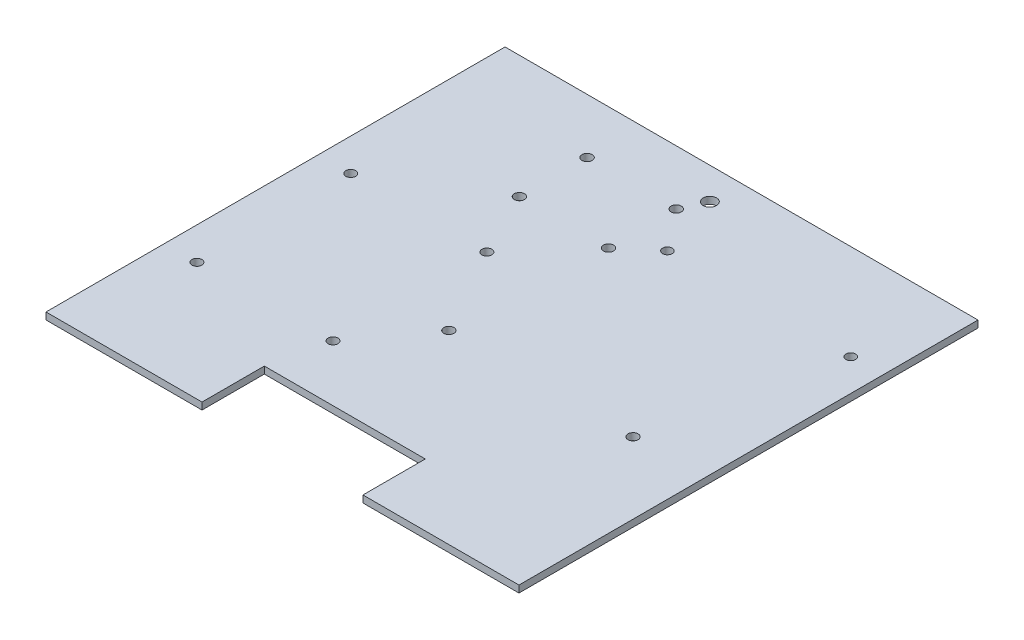
SolidWorks part; units mm, degrees
ref_plane "Front Plane" through (0, 0, 0) normal (0, 0, 1) x (1, 0, 0)
ref_plane "Top Plane" through (0, 0, 0) normal (0, 1, 0) x (1, 0, 0)
ref_plane "Right Plane" through (0, 0, 0) normal (1, 0, 0) x (0, 0, -1)
sketch "Sketch1" plane through (0, 0, 0) normal (0, 1, 0) x (1, 0, 0)
  line L1 (-94.869, -92.075) -> (94.869, -92.075)
  line L2 (-94.869, -92.075) -> (-94.869, 92.075)
  line L3 (-94.869, 92.075) -> (94.869, 92.075)
  line L4 (94.869, -92.075) -> (94.869, 92.075)
  line L5 (-94.869, -92.075) -> (94.869, 92.075) construction
  line L6 (-94.869, 92.075) -> (94.869, -92.075) construction
  point P0 (0, 0)
  dimension "D1" = 189.738
  dimension "D2" = 184.15
extrude "Boss-Extrude1" add sketch "Sketch1" along normal blind 2.794
sketch "Sketch2" plane through (0, 2.794, 0) normal (0, 1, 0) x (1, 0, 0)
  line L2 (94.869, 92.075) -> (-94.869, 92.075) construction
  circle A0 centre (0, 79.375) radius 2.6797
  point P4 (0, 92.075)
  dimension "D1" = 5.3594
  dimension "D2" = 12.7
extrude "Cut-Extrude1" cut sketch "Sketch2" against normal through all
sketch "Sketch3" plane through (0, 2.794, 0) normal (0, 1, 0) x (1, 0, 0)
  line L0 (0, -92.075) -> (-32.28, -92.075)
  line L1 (-94.869, -92.075) -> (94.869, -92.075) construction
  line L2 (-32.28, -92.075) -> (-32.28, -67.075)
  line L3 (-32.28, -67.075) -> (32.28, -67.075)
  line L4 (32.28, -67.075) -> (32.28, -92.075)
  line L5 (32.28, -92.075) -> (0, -92.075)
  point P5 (0, -67.075)
  dimension "D1" = 64.56
  dimension "D3" = 25
extrude "Cut-Extrude2" cut sketch "Sketch3" against normal through all
sketch "Sketch4" plane through (0, 2.794, 0) normal (0, 1, 0) x (1, 0, 0)
  line L7 (-42.851, 73.025) -> (-1.671, 73.025)
  line L8 (-42.851, 73.025) -> (-42.851, 40.025)
  line L9 (-42.851, 40.025) -> (-1.671, 40.025)
  line L10 (-1.671, 73.025) -> (-1.671, 40.025)
  line L11 (-42.851, 73.025) -> (-1.671, 40.025) construction
  line L12 (-42.851, 40.025) -> (-1.671, 73.025) construction
  line L13 (4.679, 79.375) -> (85.979, 79.375)
  line L14 (4.679, 79.375) -> (4.679, 28.355)
  line L15 (4.679, 28.355) -> (85.979, 28.355)
  line L16 (85.979, 79.375) -> (85.979, 28.355)
  line L17 (4.679, 79.375) -> (85.979, 28.355) construction
  line L18 (4.679, 28.355) -> (85.979, 79.375) construction
  line L19 (-42.851, 56.525) -> (-1.671, 56.525) construction
  line L20 (-85.979, -61.067) -> (-85.979, 33.675)
  line L21 (-85.979, 33.675) -> (-23.114, 33.675)
  line L22 (-23.114, 33.675) -> (-23.114, -61.067)
  line L23 (-23.114, -61.067) -> (-85.979, -61.067)
  line L24 (94.869, 92.075) -> (-94.869, 92.075) construction
  line L25 (-94.869, 92.075) -> (-94.869, -92.075) construction
  line L26 (94.869, -92.075) -> (94.869, 92.075) construction
  line L28 (-10.414, -60.725) -> (68.716, -60.725)
  line L29 (-10.414, -60.725) -> (-10.414, 11.275)
  line L30 (-10.414, 11.275) -> (68.716, 11.275)
  line L31 (68.716, -60.725) -> (68.716, 11.275)
  line L32 (-10.414, -60.725) -> (68.716, 11.275) construction
  line L33 (-10.414, 11.275) -> (68.716, -60.725) construction
  line L34 (32.28, -67.075) -> (-32.28, -67.075) construction
  circle A2 centre (8.5515, 53.7875) radius 1.9362
  circle A3 centre (82.1065, 53.7875) radius 1.9362
  circle A4 centre (-39.976, 70.1) radius 2.0487
  circle A5 centre (-4.226, 70.1) radius 2.0487
  circle A6 centre (-4.226, 42.95) radius 2.0487
  circle A7 centre (-39.976, 42.95) radius 2.0487
  circle A8 centre (-81.8515, -44.557) radius 1.9812
  circle A9 centre (-81.8515, 17.165) radius 1.9812
  circle A10 centre (-27.2415, 17.165) radius 1.9812
  circle A11 centre (-27.2415, -44.557) radius 1.9812
  circle A14 centre (66.241, -17.69) radius 2.0387
  circle A15 centre (-7.639, -17.69) radius 2.0387
  point P0 (29.151, -24.725)
  point P11 (-22.261, 56.525)
  point P16 (45.329, 53.865)
  dimension "D4" = 79.13
  dimension "D5" = 72
  dimension "D6" = 73.88
  dimension "D7" = 4.0774
  dimension "D13" = 3.8724
  dimension "D15" = 3.8724
  dimension "D20" = 4.0974
  dimension "D24" = 3.9624
  dimension "D30" = 54.61
  dimension "D31" = 61.722
  dimension "D32" = 54.61
  dimension "D33" = 6.35
  dimension "D8" = 41.18
  dimension "D9" = 33
  dimension "D10" = 81.3
  dimension "D11" = 51.02
  dimension "D12" = 12.7
  dimension "D14" = 25.4325
  dimension "D16" = 25.4325
  dimension "D17" = 3.8725
  dimension "D18" = 3.8725
  dimension "D19" = 35.75
  dimension "D21" = 2.925
  dimension "D22" = 2.555
  dimension "D23" = 16.5
  dimension "D25" = 16.51
  dimension "D26" = 4.1275
  dimension "D27" = 62.865
  dimension "D28" = 94.742
  dimension "D29" = 19.05
  dimension "D34" = 8.89
  dimension "D35" = 8.89
  dimension "D36" = 6.35
  dimension "D37" = 2.775
  dimension "D38" = 43.035
  dimension "D39" = 6.35
  dimension "D40" = 12.7
extrude "Cut-Extrude3" cut sketch "Sketch4" against normal through all contours A14 | A15 | A3 | A2 | A5 | A4 | A7 | A6 | A9 | A10 | A11 | A8
